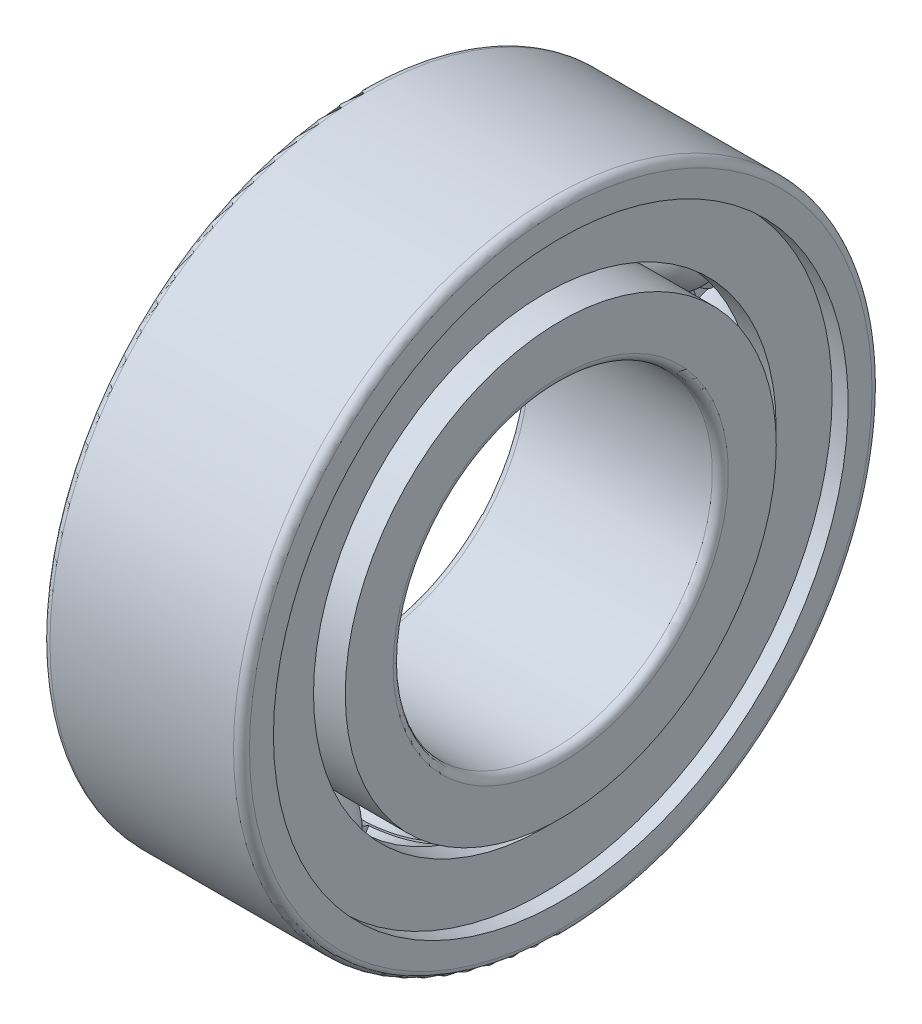
SolidWorks part; units mm, degrees
ref_plane "基准面1" through (0, 0, 0) normal (0, 0, 1) x (1, 0, 0)
ref_plane "基准面2" through (0, 0, 0) normal (0, 1, 0) x (1, 0, 0)
ref_plane "基准面3" through (0, 0, 0) normal (1, 0, 0) x (0, 0, -1)
sketch "尺寸草图" plane through (0, 0, 0) normal (0, 0, 1) x (1, 0, 0)
  point P0 (0, -75.4307)
  point P1 (2.4, -75.4307)
  point P2 (0, 50.7088)
  point P3 (8, 50.7088)
  point P4 (16, 50.7088)
  point P5 (5, 50.7088)
  point P6 (0, -10.9899)
  point P7 (10.8, -10.9899)
  point P8 (14.5, -10.9899)
  point P9 (0.2, -10.9899)
  point P10 (13, -75.4307)
  dimension "d" = 8
  dimension "DD" = 16
  dimension "B" = 5
  dimension "内圈外径DD2" = 10.8
  dimension "防尘圈径D3" = 14.5
  dimension "r" = 0.2
  dimension "球径DW" = 2.4
  dimension "球数Z" = 13
sketch "草图2" plane through (0, 0, 0) normal (0, 0, 1) x (1, 0, 0)
  line L0 (-12.4206, 0) -> (9.8128, 0) construction
  line L1 (0, 0) -> (0, 37.3563) construction
  line L2 (-5.5681, 6.3) -> (6.1049, 6.3) construction
  line L3 (-0.264, 6.63) -> (0.264, 6.63)
  line L4 (-0.264, 6.63) -> (-0.264, 5.97)
  line L5 (-0.264, 5.97) -> (0.264, 5.97)
  line L6 (0.264, 6.63) -> (0.264, 5.97)
  dimension "D1" = 0.528
  dimension "D2" = 0.264
  dimension "D3" = 0.66
  dimension "D4" = 0.33
  dimension "D5" = 6.3
revolve "基体-旋转" add sketch "草图2" angle 360 about L0
sketch "草图3" plane through (0, 0, 0) normal (0, 0, 1) x (1, 0, 0)
  line L0 (-5.5681, 6.3) -> (6.1049, 6.3) construction
  line L1 (-5.5681, 6.3) -> (6.1049, 6.3) construction
  line L2 (-12.4206, 0) -> (9.8128, 0) construction
  line L3 (-12.4206, 0) -> (9.8128, 0) construction
  line L4 (0, 0) -> (0, 37.3563) construction
  line L5 (0, 0) -> (0, 37.3563) construction
  line L6 (-1.32, 6.3) -> (1.32, 6.3)
  arc A0 (-1.32, 6.3) -> (1.32, 6.3) centre (0, 6.3) ccw
  dimension "Dwww" = 2.64
  dimension "D2" = 1.32
revolve "凸台-旋转1" add sketch "草图3" angle 360 about L1
pattern_circular "阵列(圆周)1" count 13 over 360 about axis through (-12.4206, 0, 0) along (1, 0, 0) of "凸台-旋转1"
sketch "草图4" plane through (0, 0, 0) normal (0, 0, 1) x (1, 0, 0)
  line L0 (0, 0) -> (8.1272, 0) construction
  line L1 (-12.4206, 0) -> (9.8128, 0) construction
  line L3 (-0.264, 6.63) -> (0.264, 6.63) construction
  line L4 (-1.32, 7.95) -> (1.32, 7.95)
  line L5 (-1.32, 7.95) -> (-1.32, 6.63)
  line L6 (-1.32, 6.63) -> (1.32, 6.63)
  line L7 (1.32, 7.95) -> (1.32, 6.63)
revolve "切除-旋转1" cut sketch "草图4" angle 360 about L0
sketch "草图5" plane through (0, 0, 0) normal (0, 0, 1) x (1, 0, 0)
  line L0 (0, 0) -> (8.2665, 0) construction
  line L1 (-12.4206, 0) -> (9.8128, 0) construction
  line L2 (-0.264, 5.97) -> (0.264, 5.97) construction
  line L3 (-1.32, 5.97) -> (1.32, 5.97)
  line L4 (-1.32, 5.97) -> (-1.32, 4.65)
  line L5 (-1.32, 4.65) -> (1.32, 4.65)
  line L6 (1.32, 5.97) -> (1.32, 4.65)
revolve "切除-旋转2" cut sketch "草图5" angle 360 about L0
sketch "草图6" plane through (0, 0, 0) normal (0, 0, 1) x (1, 0, 0)
  line L0 (0, 0) -> (5.5439, 0) construction
  line L1 (-12.4206, 0) -> (9.8128, 0) construction
  line L2 (0, 0) -> (0, 11.4011) construction
  line L3 (-5.5681, 6.3) -> (6.1049, 6.3) construction
  line L4 (-5.5681, 6.3) -> (6.1049, 6.3) construction
  line L5 (-1.2, 6.3) -> (1.2, 6.3)
  arc A0 (-1.2, 6.3) -> (1.2, 6.3) centre (0, 6.3) ccw
  dimension "Dw" = 2.4
revolve "凸台-旋转2" add sketch "草图6" angle 360 about L4
pattern_circular "阵列(圆周)2" count 13 over 360 about axis through (-12.4206, 0, 0) along (1, 0, 0) of "凸台-旋转2"
sketch "草图7" plane through (0, 0, 0) normal (0, 0, 1) x (1, 0, 0)
  line L0 (0, 0) -> (6.6488, 0) construction
  line L1 (0, 0) -> (0, 16.8954) construction
  line L2 (-2.3, 8) -> (2.3, 8)
  line L3 (-2.5, 7.8) -> (-2.5, 7.2)
  line L4 (-2.5, 7.2) -> (-0.7785, 7.2)
  line L5 (2.5, 7.8) -> (2.5, 7.2)
  line L6 (0.7785, 7.2) -> (1.5648, 7.2)
  line L7 (2.1, 7.2) -> (2.5, 7.2)
  line L8 (1.5648, 7.25) -> (2.1, 7.25)
  line L9 (1.5648, 7.25) -> (1.5648, 7.2)
  line L11 (2.1, 7.25) -> (2.1, 7.2)
  arc A0 (-2.3, 8) -> (-2.5, 7.8) centre (-2.3, 7.8) ccw
  arc A1 (2.3, 8) -> (2.5, 7.8) centre (2.3, 7.8) cw
  arc A2 (1.1537, 6.63) -> (-1.1537, 6.63) centre (0, 6.3) ccw construction
  arc A3 (0.7937, 7.2) -> (0, 7.5) centre (0, 6.3) ccw construction
  arc A4 (0.7785, 7.2) -> (-0.7785, 7.2) centre (0, 6.3) ccw
  point P10 (-2.5, 8)
  point P13 (2.5, 8)
  dimension "R" = 0.2
  dimension "D1" = 0.01
  dimension "D2" = 14.4
  dimension "D" = 16
  dimension "D3" = 2.5
  dimension "B" = 5
  dimension "D4" = 0.5352
  dimension "D5" = 14.5
  dimension "D6" = 0.4
revolve "凸台-旋转3" add sketch "草图7" angle 360 about L0
sketch "草图8" plane through (0, 0, 0) normal (0, 0, 1) x (1, 0, 0)
  line L0 (-12.4206, 0) -> (9.8128, 0) construction
  line L1 (-12.4206, 0) -> (9.8128, 0) construction
  line L2 (2.5, 7.8) -> (2.5, 7.2) construction
  line L3 (-2.5, 5.4) -> (-0.7785, 5.4)
  line L4 (-2.5, 5.4) -> (-2.5, 4.2)
  line L5 (-2.3, 4) -> (2.3, 4)
  line L6 (2.5, 5.4) -> (2.5, 4.2)
  line L7 (-2.5, 7.8) -> (-2.5, 7.2) construction
  line L8 (0.7785, 5.4) -> (2.5, 5.4)
  arc A0 (-2.5, 4.2) -> (-2.3, 4) centre (-2.3, 4.2) ccw
  arc A1 (2.3, 4) -> (2.5, 4.2) centre (2.3, 4.2) ccw
  arc A2 (-1.1537, 5.97) -> (1.1537, 5.97) centre (0, 6.3) ccw construction
  arc A3 (-1.1537, 5.97) -> (1.1537, 5.97) centre (0, 6.3) ccw construction
  arc A4 (-0.7785, 5.4) -> (0.7785, 5.4) centre (0, 6.3) ccw
  dimension "D1" = 0.2
  dimension "DD" = 8
  dimension "D2" = 0.01
  dimension "DD2" = 10.8
revolve "凸台-旋转4" add sketch "草图8" angle 360 about L1
sketch "草图10" plane through (0, 0, 0) normal (0, 0, 1) x (1, 0, 0)
  line L0 (1.5648, -7.2) -> (1.5648, 7.2) construction
  line L1 (2.1, 7.25) -> (1.5648, 7.25)
  line L2 (2.1, 7.25) -> (2.1, 5.796)
  line L3 (2.1, 5.796) -> (1.5648, 5.796)
  line L4 (1.5648, 7.25) -> (1.5648, 5.796)
  line L5 (0.7785, 5.4) -> (2.5, 5.4) construction
  line L6 (0, 0) -> (-5.3515, 0) construction
  line L7 (-12.4206, 0) -> (9.8128, 0) construction
  dimension "D1" = 0.396
revolve "凸台-旋转5" add sketch "草图10" angle 360 about L6
sketch "草图11" plane through (0, 0, 0) normal (1, 0, 0) x (0, 0, -1)
  circle A0 centre (0, 0) radius 8
  circle A1 centre (0, 0) radius 8 construction
extrude "切除-拉伸1" cut sketch "草图11" against normal blind 10
mirror "镜向所有1" about plane through (0, 0, 0) normal (1, 0, 0) of bodies 109
equation "\"D5@草图7\" = \"防尘圈径D3@尺寸草图\""
equation "\"Z@阵列(圆周)1\"=\"球数Z@尺寸草图\" "
equation "\"Dw@草图6\"=\"球径DW@尺寸草图\""
equation "\"DD@草图8\"=\"d@尺寸草图\""
equation "\"D@草图7\"=\"DD@尺寸草图\""
equation "\"B@草图7\"=\"B@尺寸草图\" "
equation "\"DD2@草图8\"=\"内圈外径DD2@尺寸草图\""
equation "\"R@草图7\"=\"r@尺寸草图\""
equation "\"D3@草图2\" = 0.25*\"Dwww@草图3\""
equation "\"D4@草图2\" = \"D3@草图2\"/2"
equation "\"Dwww@草图3\" = 1.1*\"Dw@草图6\""
equation "\"D2@草图3\" = 0.5*\"Dwww@草图3\""
equation "\"D1@草图2\" = 0.2*\"Dwww@草图3\""
equation "\"D2@草图2\" = 0.5*\"D1@草图2\""
equation "\"切除位置@草图4\" = \"Dwww@草图3\"/2"
equation "\"D1@阵列(圆周)2\" = \"Z@阵列(圆周)1\""
equation "\"D3@草图7\" = \"B@草图7\" / 2"
equation "\"D1@草图8\" = \"R@草图7\""
equation "\"D2@草图7\" = 0.9*\"D@草图7\""
equation "\"D5@草图2\" = 0.25* ( \"D2@草图7\" + \"DD2@草图8\" )  "
equation "\"D6@草图7\" = 0.08 * \"B@草图7\""
equation "\"D1@草图10\" = 0.15*\"Dwww@草图3\""
